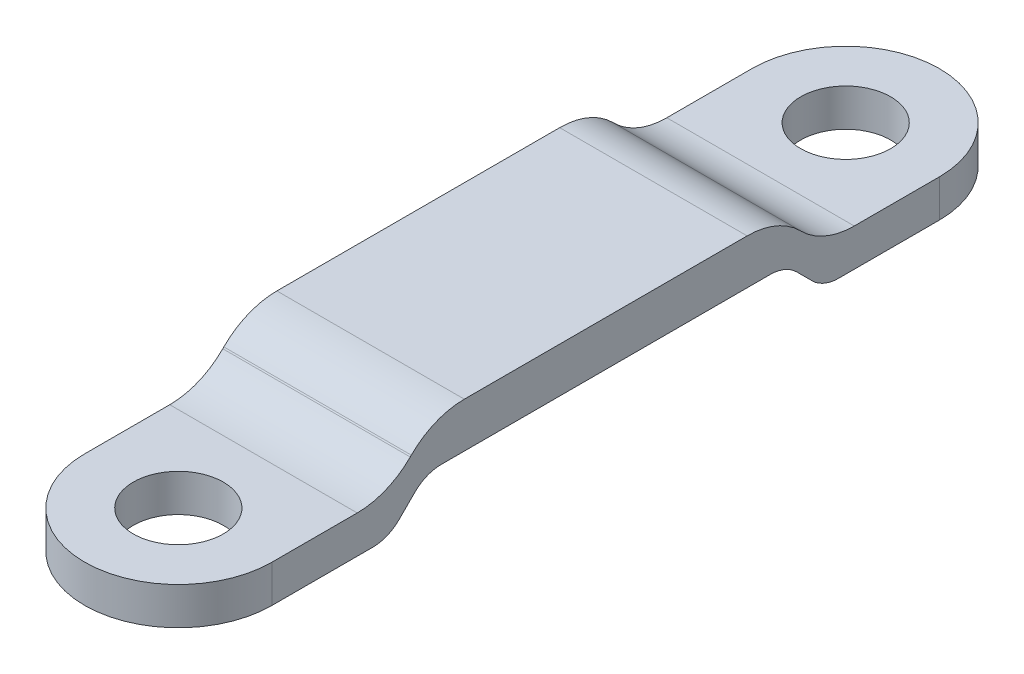
SolidWorks part; units mm, degrees
ref_plane "Front Plane" through (0, 0, 0) normal (0, 0, 1) x (1, 0, 0)
ref_plane "Top Plane" through (0, 0, 0) normal (0, 1, 0) x (1, 0, 0)
ref_plane "Right Plane" through (0, 0, 0) normal (1, 0, 0) x (0, 0, -1)
sketch "Sketch1" plane through (0, 0, 0) normal (1, 0, 0) x (0, 0, -1)
  line L0 (0, 11) -> (0, 5)
  line L1 (57, 0) -> (57, 5)
  line L2 (57, 5) -> (33.1421, 5)
  line L3 (57, 0) -> (31.0711, 0)
  line L4 (27.5355, 1.4645) -> (25.4645, 3.5355)
  line L5 (-18.8579, 11) -> (18.8579, 11)
  line L6 (26.0711, 7.9289) -> (25.9289, 8.0711)
  line L7 (21.9289, 5) -> (-21.9289, 5)
  line L8 (0, 11) -> (0, 0) construction
  line L9 (-26.0711, 7.9289) -> (-25.9289, 8.0711)
  line L10 (-27.5355, 1.4645) -> (-25.4645, 3.5355)
  line L11 (-57, 0) -> (-31.0711, 0)
  line L12 (-57, 5) -> (-33.1421, 5)
  line L13 (-57, 0) -> (-57, 5)
  arc A0 (31.0711, 0) -> (27.5355, 1.4645) centre (31.0711, 5) cw
  arc A1 (21.9289, 5) -> (25.4645, 3.5355) centre (21.9289, 0) cw
  arc A2 (33.1421, 5) -> (26.0711, 7.9289) centre (33.1421, 15) cw
  arc A3 (18.8579, 11) -> (25.9289, 8.0711) centre (18.8579, 1) cw
  arc A4 (-18.8579, 11) -> (-25.9289, 8.0711) centre (-18.8579, 1) ccw
  arc A5 (-33.1421, 5) -> (-26.0711, 7.9289) centre (-33.1421, 15) ccw
  arc A6 (-21.9289, 5) -> (-25.4645, 3.5355) centre (-21.9289, 0) ccw
  arc A7 (-31.0711, 0) -> (-27.5355, 1.4645) centre (-31.0711, 5) ccw
  point P14 (29, 0)
  point P19 (29, 5)
  point P34 (-29, 5)
  point P35 (-29, 0)
  dimension "D7" = 5
  dimension "D8" = 10
  dimension "D1" = 57
  dimension "D2" = 5
  dimension "D3" = 28
  dimension "D4" = 28
  dimension "D5" = 6
  dimension "D6" = 135
extrude "Boss-Extrude2" add sketch "Sketch1" along normal mid plane 25 contours L11 A7 L10 A6 L7 L0 L5 A4 L9 A5 L12 L13 | A3 L5 L0 L7 A1 L4 A0 L3 L1 L2 A2 L6 region at (0, 5.2308, -27.2604) region at (0, 5.2308, 27.2604)
sketch "Sketch2" plane through (0, 5, 0) normal (0, 1, 0) x (1, 0, 0)
  line L2 (0, 0) -> (12.5, 0) construction
  line L3 (12.5, -18.8579) -> (12.5, 18.8579) construction
  circle A0 centre (0, 44.5) radius 6
  circle A1 centre (0, -44.5) radius 6
  dimension "D2" = 12
  dimension "D1" = 44.5
extrude "Cut-Extrude1" cut sketch "Sketch2" against normal through all
fillet "Fillet1" 2 edges at (12.5, 2.5, -57) (-12.5, 2.5, -57) type full round first side face at (12.5, 4.7, 0) second side face at (-12.5, 4.7, 0) middle face at (0, 2.5, -57)
fillet "Fillet2" 2 edges at (12.5, 2.5, 57) (-12.5, 2.5, 57) type full round first side face at (12.5, 4.7, 1.25) second side face at (-12.5, 4.7, 1.25) middle face at (0, 2.5, 57)
